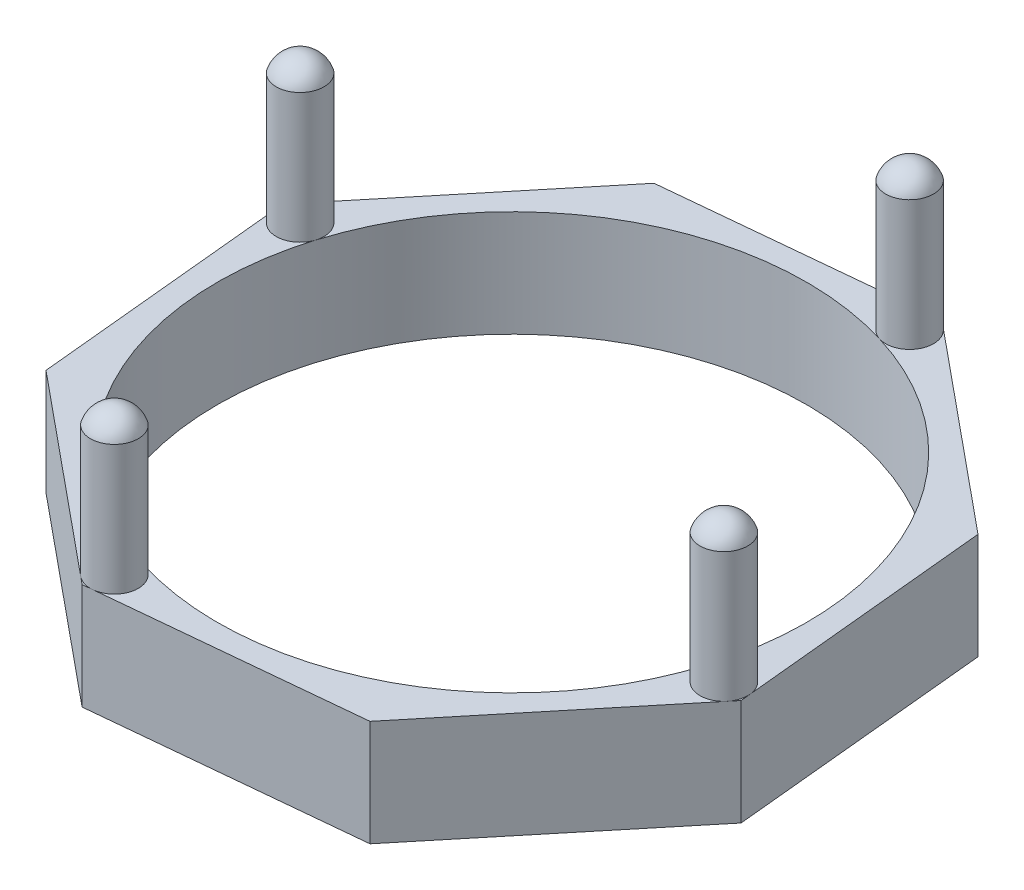
SolidWorks part; units mm, degrees
ref_plane "Front Plane" through (0, 0, 0) normal (0, 0, 1) x (1, 0, 0)
ref_plane "Top Plane" through (0, 0, 0) normal (0, 1, 0) x (1, 0, 0)
ref_plane "Right Plane" through (0, 0, 0) normal (1, 0, 0) x (0, 0, -1)
sketch "Sketch1" plane through (0, 0, 0) normal (0, 1, 0) x (1, 0, 0)
  line L0 (-27.4876, 51.5823) -> (-55.9109, 17.0375)
  line L1 (-51.5823, -27.4876) -> (-17.0375, -55.9109)
  line L2 (-17.0375, -55.9109) -> (27.4876, -51.5823)
  line L3 (27.4876, -51.5823) -> (55.9109, -17.0375)
  line L4 (55.9109, -17.0375) -> (51.5823, 27.4876)
  line L5 (51.5823, 27.4876) -> (17.0375, 55.9109)
  line L6 (17.0375, 55.9109) -> (-27.4876, 51.5823)
  line L7 (-55.9109, 17.0375) -> (-51.5823, -27.4876)
  circle A0 centre (0, 0) radius 50
  circle A1 centre (0, 0) radius 54 construction
extrude "Boss-Extrude1" add sketch "Sketch1" along normal blind 18
sketch "Sketch2" plane through (0, 18, 0) normal (0, 1, 0) x (1, 0, 0)
  line L0 (-27.4876, 51.5823) -> (-55.9109, 17.0375) construction
  line L2 (-55.9109, 17.0375) -> (-51.5823, -27.4876) construction
  circle A0 centre (-51.7099, 15.7574) radius 4.0574
  circle A1 centre (0, 0) radius 50 construction
  circle A2 centre (15.7574, 51.7099) radius 4.0574
  circle A3 centre (51.7099, -15.7574) radius 4.0574
  circle A4 centre (-15.7574, -51.7099) radius 4.0574
  point P17 (0, 0)
  dimension "D1" = 4
extrude "Boss-Extrude2" add sketch "Sketch2" along normal blind 22
dome "Dome1" faces to dome 1 distance 3 reverse direction no elliptical dome no face at (-51.7099, 40, -11.6999) parameters "D1"=3
dome "Dome2" faces to dome 1 distance 3 reverse direction no elliptical dome no face at (15.7574, 40, -47.6524) parameters "D1"=3
dome "Dome3" faces to dome 1 distance 3 reverse direction no elliptical dome no face at (51.7099, 40, 19.8148) parameters "D1"=3
dome "Dome4" faces to dome 1 distance 3 reverse direction no elliptical dome no face at (-15.7574, 40, 55.7673) parameters "D1"=3
